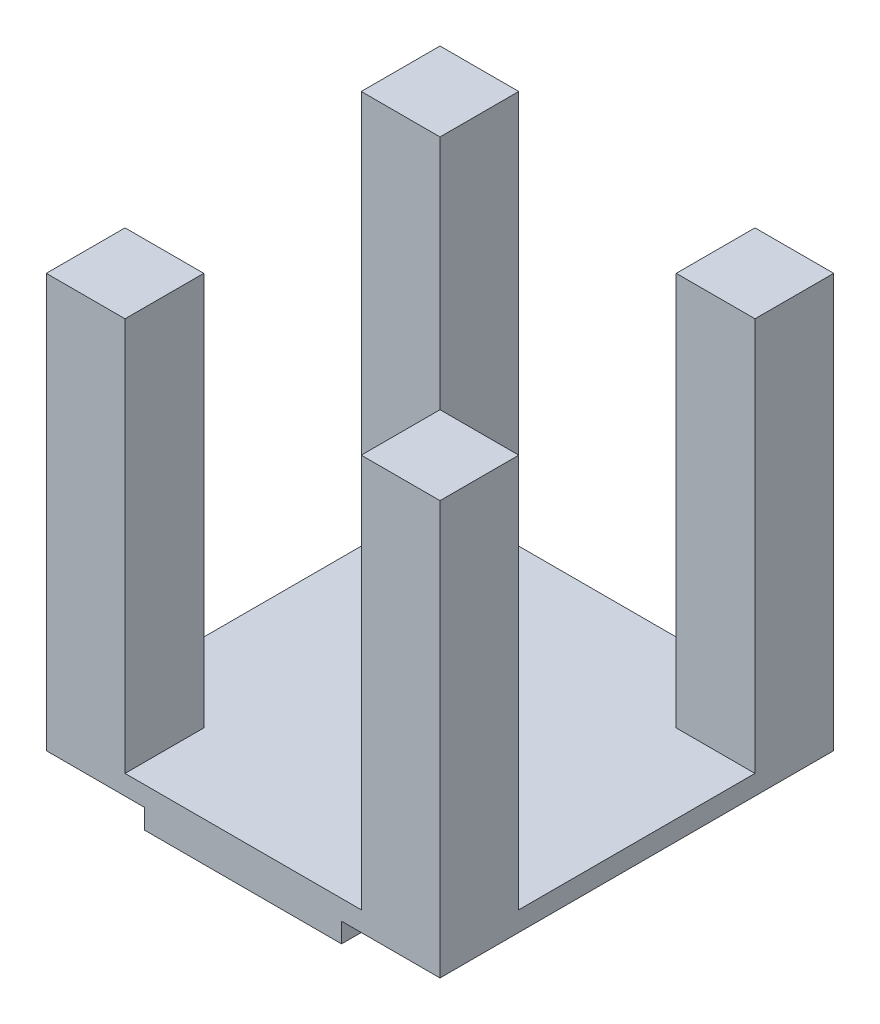
SolidWorks part; units mm, degrees
ref_plane "Front Plane" through (0, 0, 0) normal (0, 0, 1) x (1, 0, 0)
ref_plane "Top Plane" through (0, 0, 0) normal (0, 1, 0) x (1, 0, 0)
ref_plane "Right Plane" through (0, 0, 0) normal (1, 0, 0) x (0, 0, -1)
sketch "Sketch1" plane through (0, 0, 0) normal (0, 1, 0) x (1, 0, 0)
  line L1 (-500, 500) -> (500, 500)
  line L2 (-500, 500) -> (-500, -500)
  line L3 (-500, -500) -> (500, -500)
  line L4 (500, 500) -> (500, -500)
  line L5 (-500, 500) -> (500, -500) construction
  line L6 (-500, -500) -> (500, 500) construction
  point P0 (0, 0)
  dimension "D1" = 1000
  dimension "D2" = 1000
extrude "Boss-Extrude1" add sketch "Sketch1" along normal blind 50
sketch "Sketch2" plane through (0, 50, 0) normal (0, 1, 0) x (1, 0, 0)
  line L1 (-500, 500) -> (-300, 500)
  line L2 (-500, 500) -> (-500, 300)
  line L3 (-500, 300) -> (-300, 300)
  line L4 (-300, 500) -> (-300, 300)
  dimension "D1" = 200
  dimension "D2" = 200
extrude "Boss-Extrude2" add sketch "Sketch2" along normal blind 1000
mirror "Mirror1" about plane through (0, 0, 0) normal (0, 0, 1) of "Boss-Extrude2"
mirror "Mirror2" about plane through (0, 0, 0) normal (0, 0, 1) of "Boss-Extrude2" second plane through (0, 0, 0) second plane normal (1, 0, 0)
ref_plane "Plane1" through (-300, 50, 300) normal (0, 0, 1) x (1, 0, 0)
sketch "Sketch4" plane through (0, 0, 0) normal (0, -1, 0) x (1, 0, 0)
  line L0 (0, -27.5) -> (0, 27.5) construction
  line L13 (-250, 500) -> (250, 500)
  line L14 (-250, 500) -> (-250, 0)
  line L15 (-250, 0) -> (250, 0)
  line L16 (250, 500) -> (250, 0)
  line L17 (-250, 500) -> (250, 0) construction
  line L18 (-250, 0) -> (250, 500) construction
  point P0 (0, 250)
  dimension "D1" = 500
  dimension "D2" = 500
  dimension "D3" = 250
extrude "Boss-Extrude4" add sketch "Sketch4" along normal blind 50
sketch "Sketch5" plane through (0, 0, 0) normal (0, -1, 0) x (1, 0, 0)
  line L0 (0, -550) -> (0, 550) construction
  circle A0 centre (0, -275.6543) radius 74.5
  dimension "D1" = 149
